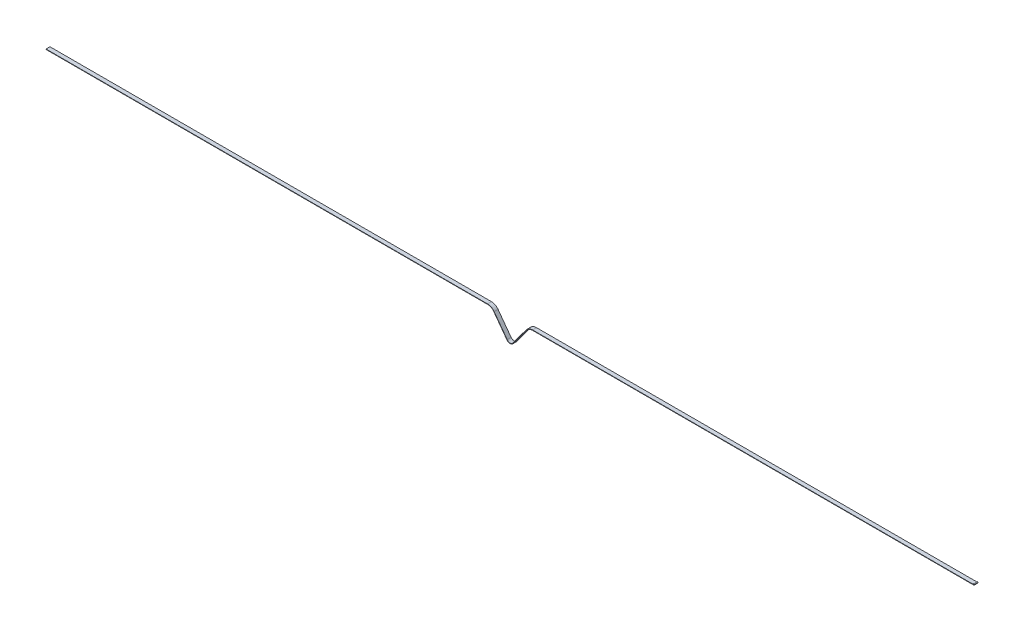
SolidWorks part; units mm, degrees
ref_plane "Front Plane" through (0, 0, 0) normal (0, 0, 1) x (1, 0, 0)
ref_plane "Top Plane" through (0, 0, 0) normal (0, 1, 0) x (1, 0, 0)
ref_plane "Right Plane" through (0, 0, 0) normal (1, 0, 0) x (0, 0, -1)
sketch "Sketch1" plane through (0, 0, 0) normal (1, 0, 0) x (0, 0, -1)
  line L1 (0, 0) -> (6, 0)
  line L2 (0, 0) -> (0, 0.63)
  line L3 (0, 0.63) -> (6, 0.63)
  line L4 (6, 0) -> (6, 0.63)
  dimension "D1" = 0.63
  dimension "D2" = 6
sketch "Sketch2" plane through (0, 0, 0) normal (0, 0, 1) x (1, 0, 0)
  line L0 (0, 0) -> (-676.5638, 0)
  line L1 (-686.1964, -4.8779) -> (-706.2086, -32.1359)
  line L2 (-716.0589, -32.1359) -> (-736.0711, -4.8779)
  line L3 (-745.7038, 0) -> (-1422.4, 0)
  arc A0 (-676.5638, 0) -> (-686.1964, -4.8779) centre (-676.5638, -11.95) ccw
  arc A1 (-706.2086, -32.1359) -> (-716.0589, -32.1359) centre (-711.1338, -28.52) cw
  arc A2 (-736.0711, -4.8779) -> (-745.7038, 0) centre (-745.7038, -11.95) ccw
  circle A3 centre (-745.7038, -11.95) radius 11.95 construction
  circle A4 centre (-711.1338, -28.52) radius 6.11 construction
  circle A5 centre (-676.5638, -11.95) radius 11.95 construction
  dimension "D1" = 6.11
  dimension "D4" = 1422.4
sweep "Sweep1" add profiles "Sketch1" path "Sketch2"
sketch "Sketch3" plane through (0, 0, 0) normal (0, 0, 1) x (1, 0, 0)
  line L0 (0, 0.63) -> (-676.5638, 0.63) construction
  line L1 (-1.5, 0.63) -> (-1.5, 0)
  line L2 (0, 0) -> (-676.5638, 0) construction
  line L3 (-1.5, 0) -> (0, 0)
  line L4 (0, 0) -> (0, 0.63)
  arc A1 (0, 0.63) -> (-1.5, 0.63) centre (-0.75, 0.63) ccw
  dimension "D1" = 0.75
extrude "Boss-Extrude1" add sketch "Sketch3" against normal through all
pattern_curve "CrvPattern1" [suppressed] of bodies 102 driven by "Sketch2" parameters "D1"=2000, "D3"=2, "D2"=1, "D4"=10
